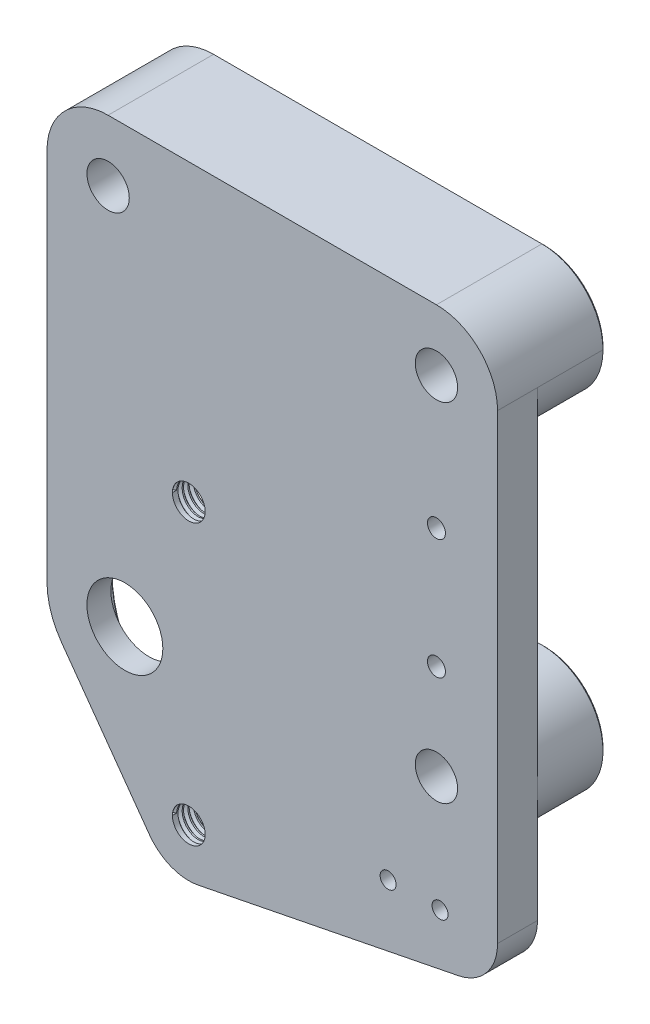
SolidWorks part; units mm, degrees
ref_plane "Front Plane" through (0, 0, 0) normal (0, 0, 1) x (1, 0, 0)
ref_plane "Top Plane" through (0, 0, 0) normal (0, 1, 0) x (1, 0, 0)
ref_plane "Right Plane" through (0, 0, 0) normal (1, 0, 0) x (0, 0, -1)
sketch "Sketch1" plane through (0, 0, 0) normal (0, 0, 1) x (1, 0, 0)
  line L0 (-41.1, 21.74) -> (0, 21.74) construction
  line L1 (0, 21.74) -> (0, -21.74) construction
  line L2 (-31, -25) -> (-39, -25) construction
  line L3 (-41, -23.5) -> (-37, -23.5) construction
  line L4 (-31, -25) -> (-12, -25) construction
  line L5 (-31, -25) -> (-31, -17.5) construction
  line L6 (-31, -17.5) -> (-12, -17.5) construction
  line L7 (-12, -25) -> (-12, -17.5) construction
  line L8 (-31, -25) -> (-12, -25) construction
  line L9 (-31, -25) -> (-31, -32.5) construction
  line L10 (-31, -32.5) -> (-12, -32.5) construction
  line L11 (-12, -25) -> (-12, -32.5) construction
  line L12 (-41, -26.5) -> (-37, -26.5) construction
  line L13 (-31, -42.5) -> (-31, -7.5) construction
  line L14 (-27.5, -7.5) -> (-27.5, -11.4446) construction
  line L15 (-34.5, -7.5) -> (-34.5, -11.4446) construction
  line L16 (-27.5, -42.5) -> (-27.5, -38.5554) construction
  line L17 (-34.5, -42.5) -> (-34.5, -38.5554) construction
  line L18 (0, -12.5249) -> (0, 12.4751) construction
  line L19 (-6, -12.5249) -> (6, -12.5249) construction
  line L20 (-6, -12.5249) -> (-6, 12.4751) construction
  line L21 (-6, 12.4751) -> (6, 12.4751) construction
  line L22 (6, -12.5249) -> (6, 12.4751) construction
  line L23 (-16.5, 74.5503) -> (-16.5, -75.4497) construction
  line L24 (-1.6, 12.4751) -> (1.6, 12.4751) construction
  line L25 (-1.6, 12.4751) -> (-1.6, 18.1751) construction
  line L26 (-1.6, 18.1751) -> (1.6, 18.1751) construction
  line L27 (1.6, 12.4751) -> (1.6, 18.1751) construction
  line L28 (-1.5, -12.5249) -> (1.5, -12.5249) construction
  line L29 (-1.5, -12.5249) -> (-1.5, -18.1749) construction
  line L30 (-1.5, -18.1749) -> (1.5, -18.1749) construction
  line L31 (1.5, -12.5249) -> (1.5, -18.1749) construction
  line L32 (6, 6.5051) -> (13.5, 6.5051) construction
  line L33 (6, 6.5051) -> (6, 10.9051) construction
  line L34 (6, 10.9051) -> (13.5, 10.9051) construction
  line L35 (13.5, 6.5051) -> (13.5, 10.9051) construction
  line L36 (-50, -10) -> (50, -10) construction
  line L37 (-50, -10) -> (-50, 10) construction
  line L38 (-50, 10) -> (50, 10) construction
  line L39 (50, -10) -> (50, 10) construction
  line L40 (-50, -10) -> (50, 10) construction
  line L41 (-50, 10) -> (50, -10) construction
  line L42 (-24, 74.5503) -> (-9, 74.5503) construction
  line L43 (-24, 74.5503) -> (-24, -75.4497) construction
  line L44 (-24, -75.4497) -> (-9, -75.4497) construction
  line L45 (-9, 74.5503) -> (-9, -75.4497) construction
  line L46 (-41.1, 29.39) -> (0, 29.39)
  line L47 (-35.916, -46.0264) -> (-46.9224, -30.6831)
  line L48 (-48.75, -25) -> (-48.75, 21.74)
  line L49 (-27.8523, -47.6667) -> (3.9802, -28.273)
  line L50 (7.65, 21.74) -> (7.65, -21.74)
  line L51 (-48.75, 14.09) -> (7.65, 14.09) construction
  line L52 (-7.05, -34.9931) -> (-7.05, -40.9931)
  line L53 (-7.05, -40.9931) -> (7.65, -40.9931)
  line L54 (7.65, -40.9931) -> (7.65, -12.4946)
  line L55 (0.45, -35.9931) -> (-6.05, -35.9931) construction
  line L56 (-29.8216, -48.4341) -> (7.65, -40.9931)
  circle A0 centre (-41.1, 21.74) radius 12 construction
  circle A1 centre (-41.1, 21.74) radius 2.65
  circle A2 centre (0, 21.74) radius 12 construction
  circle A3 centre (0, 21.74) radius 2.65
  circle A4 centre (0, -21.74) radius 12 construction
  circle A5 centre (0, -21.74) radius 2.65
  circle A6 centre (-31, -25) radius 14 construction
  circle A7 centre (-39, -25) radius 4.75
  circle A8 centre (-39, -25) radius 2.5 construction
  circle A9 centre (-31, -7.5) radius 2.05
  circle A10 centre (-31, -7.5) radius 3.5 construction
  circle A11 centre (-31, -42.5) radius 3.5 construction
  circle A12 centre (-31, -42.5) radius 2.05
  circle A13 centre (-39, -25) radius 15 construction
  circle A14 centre (0, -9.8249) radius 1 construction
  circle A15 centre (0, 5.1751) radius 1 construction
  circle A16 centre (-41.1, 21.74) radius 7.65
  circle A17 centre (0, 21.74) radius 7.65
  circle A18 centre (0, -21.74) radius 7.65
  circle A20 centre (-31, -42.5) radius 6.05
  circle A21 centre (-39, -25) radius 9.75
  circle A22 centre (-6.05, -35.9931) radius 1
  circle A23 centre (0.45, -35.9931) radius 1
  point P11 (0, 0)
  point P58 (6, 8.7051)
  point P66 (28.1399, 46.8209)
  dimension "D1" = 24
  dimension "D2" = 5.3
  dimension "D3" = 24
  dimension "D4" = 5.3
  dimension "D5" = 24
  dimension "D6" = 5.3
  dimension "D7" = 43.48
  dimension "D9" = 28
  dimension "D13" = 9.5
  dimension "D14" = 5
  dimension "D16" = 4.1
  dimension "D17" = 7
  dimension "D32" = 30
  dimension "D35" = 2
  dimension "D45" = 2
  dimension "D8" = 41.1
  dimension "D10" = 8
  dimension "D11" = 7.5
  dimension "D12" = 19
  dimension "D15" = 1.5
  dimension "D18" = 17.5
  dimension "D19" = 12
  dimension "D20" = 25
  dimension "D21" = 3.2
  dimension "D22" = 5.7
  dimension "D23" = 3
  dimension "D24" = 5.65
  dimension "D25" = 7.5
  dimension "D26" = 4.4
  dimension "D27" = 3.77
  dimension "D28" = 20
  dimension "D29" = 100
  dimension "D30" = 15
  dimension "D31" = 15
  dimension "D33" = 13
  dimension "D34" = 28
  dimension "D36" = 150
  dimension "D37" = 18.1751
  dimension "D42" = 39
  dimension "D43" = 14.7
  dimension "D44" = 6
  dimension "D46" = 1
  dimension "D47" = 5
  dimension "D38" = 5
  dimension "D39" = 5
  dimension "D40" = 4
  dimension "D41" = 5
extrude "Boss-Extrude1" add sketch "Sketch1" along normal blind 5 contours A21 L47 A20 L49 A18 L50 A17 L46 A16 L48 A9 | A16 A1 | A17 A3 | A18 A5 | A20 A12 | A21 A7 | A18 L49 L52 L53 L54 | L49 A20 L56 L53 L52 region at (-20.5785, -3.8476, 0) region at (-35.8436, 26.9964, 0) region at (5.2564, 26.9964, 0) region at (-39, -15.5258, 0) region at (6.4811, -25.3806, 0) region at (1.6273, -35.2213, 0) region at (-32.7998, -36.9034, 0) region at (-12.0976, -42.3056, 0)
sketch "Sketch2" plane through (0, 0, 0) normal (0, 0, -1) x (-1, 0, 0)
  line L0 (48.75, 14.09) -> (-7.65, 14.09) construction
  line L1 (48.75, 14.09) -> (-7.65, 14.09)
  circle A0 centre (0, -21.74) radius 7.65 construction
  circle A1 centre (31, -42.5) radius 2.05
  circle A2 centre (31, -42.5) radius 2.05
  circle A3 centre (39, -25) radius 4.75
  circle A4 centre (39, -25) radius 4.75
  circle A5 centre (0, -21.74) radius 2.65
  circle A6 centre (0, -21.74) radius 2.65
  circle A7 centre (0, 21.74) radius 2.65
  circle A8 centre (0, 21.74) radius 2.65
  circle A9 centre (41.1, 21.74) radius 2.65
  circle A10 centre (41.1, 21.74) radius 2.65
  circle A11 centre (31, -7.5) radius 2.05
  circle A12 centre (31, -7.5) radius 2.05
  circle A13 centre (0, -21.74) radius 7.65
  line M7 (48.75, -25) -> (48.75, 21.74)
  arc M8 (48.75, 21.74) -> (41.1, 29.39) centre (41.1, 21.74) ccw
  line M9 (41.1, 29.39) -> (0, 29.39)
  arc M10 (0, 29.39) -> (-7.65, 21.74) centre (0, 21.74) ccw
  line M11 (-7.65, 21.74) -> (-7.65, -40.9931)
  circle M18 centre (41.1, 21.74) radius 2.65
  circle M19 centre (0, 21.74) radius 2.65
  circle M20 centre (0, -21.74) radius 2.65
  dimension "D1" = 0
  dimension "D2" = 0
  dimension "D3" = 0
  dimension "D4" = 0
  dimension "D5" = 0
  dimension "D6" = 0
extrude "Boss-Extrude2" add sketch "Sketch2" along normal blind 8.5 contours L1 M7 M8 M9 M10 M11 M19 M18 | A13 M20 region at (0, -14.3064, 0) region at (-20.55, 21.552, 0)
sketch "Sketch7" plane through (0, 0, 0) normal (0, 0, -1) x (-1, 0, 0)
  line L0 (27.5, -42.5) -> (27.5, -38.5554) construction
  line L1 (34.5, -42.5) -> (34.5, -38.5554) construction
  line L2 (27.5, -7.5) -> (27.5, -11.4446) construction
  line L3 (34.5, -7.5) -> (34.5, -11.4446) construction
  line L4 (27.5, -42.5) -> (27.5, -38.5554)
  line L5 (34.5, -42.5) -> (34.5, -38.5554)
  line L6 (27.5, -7.5) -> (27.5, -11.4446)
  line L7 (34.5, -7.5) -> (34.5, -11.4446)
  line L12 (12, -25) -> (12, -32.5) construction
  line L13 (31, -32.5) -> (12, -32.5) construction
  line L14 (12, -25) -> (12, -17.5) construction
  line L15 (31, -17.5) -> (12, -17.5) construction
  line L16 (12, -25) -> (12, -32.5)
  line L17 (19.1784, -32.5) -> (12, -32.5)
  line L18 (12, -25) -> (12, -17.5)
  line L19 (19.1784, -17.5) -> (12, -17.5)
  line L20 (19.0146, -17.2) -> (11.7, -17.2)
  line L21 (11.7, -25) -> (11.7, -17.2)
  line L22 (11.7, -25) -> (11.7, -32.8)
  line L23 (19.0146, -32.8) -> (11.7, -32.8)
  line L24 (27.2, -42.5) -> (27.2, -38.7859)
  line L25 (34.8, -42.5) -> (34.8, -38.7859)
  line L26 (34.8, -7.5) -> (34.8, -11.2141)
  line L27 (27.2, -7.5) -> (27.2, -11.2141)
  circle A0 centre (31, -42.5) radius 3.5 construction
  circle A1 centre (31, -7.5) radius 3.5 construction
  circle A2 centre (31, -25) radius 14 construction
  arc A3 (27.5, -42.5) -> (34.5, -42.5) centre (31, -42.5) ccw
  arc A4 (34.5, -7.5) -> (27.5, -7.5) centre (31, -7.5) ccw
  arc A5 (34.5, -38.5554) -> (34.5, -11.4446) centre (31, -25) ccw
  arc A6 (27.5, -11.4446) -> (19.1784, -17.5) centre (31, -25) ccw
  arc A11 (19.1784, -32.5) -> (27.5, -38.5554) centre (31, -25) ccw
  arc A12 (27.2, -11.2141) -> (19.0146, -17.2) centre (31, -25) ccw
  arc A13 (19.0146, -32.8) -> (27.2, -38.7859) centre (31, -25) ccw
  arc A14 (27.2, -42.5) -> (34.8, -42.5) centre (31, -42.5) ccw
  arc A15 (34.8, -38.7859) -> (34.8, -11.2141) centre (31, -25) ccw
  arc A16 (34.8, -7.5) -> (27.2, -7.5) centre (31, -7.5) ccw
  circle M9 centre (31, -7.5) radius 2.05
  circle M10 centre (31, -42.5) radius 2.05
  circle M11 centre (39, -25) radius 4.75
  dimension "D1" = 0.3
extrude "Cut-Extrude1" cut sketch "Sketch7" against normal blind 2 contours L6 A6 L4 A3 L5 A5 L7 A4 M10 M11 M9 | A12 L19 A6 L6 A4 L7 A5 L5 A3 L4 region at (-28.1953, -25, 0) region at (-22.5909, -13.5009, 0)
fillet "Fillet1" radius 2 8 edges at (-19.0146, -32.8, 1) (-34.8, -38.7859, 1) (-27.2, -38.7859, 1) (-34.8, -11.2141, 1) (-27.2, -11.2141, 1) (-19.0146, -17.2, 1) (-11.7, -32.8, 1) (-11.7, -17.2, 1)
thread "Thread1" pitch 0.7 method cut profile "Thread Profile1" start angle 0, offset 0, length 10, pitch 0.7, diameter 4.1
ref_plane "Plane1" through (-33.05, -7.5, 5) normal (0, -1, 0) x (-1, 0, 0)
sketch "Thread Profile1" plane through (-33.05, -7.5, 5) normal (0, -1, 0) x (-1, 0, 0)
  line L0 (0, 0) -> (0, 0.7) construction
  line L1 (0, 0) -> (0.3789, 0.2187)
  line L2 (0.3789, 0.2187) -> (0.3789, 0.3062)
  line L3 (0.3789, 0.3062) -> (0, 0.525)
  line L4 (0.3789, 0.2625) -> (0, 0.2625) construction
  line L11 (0, 0) -> (0, 0.525)
  point P2 (0, 0)
  dimension "Pitch" = 0.7
  dimension "Profile_Angle" = 60
  dimension "Profile_Land" = 0.0875
  dimension "Profile_Height" = 0.3789
thread "Thread2" pitch 0.7 method cut profile "Thread Profile2" start angle 0, offset 0, length 10, pitch 0.7, diameter 4.1
ref_plane "Plane2" through (-33.05, -42.5, 5) normal (0, -1, 0) x (-1, 0, 0)
sketch "Thread Profile2" plane through (-33.05, -42.5, 5) normal (0, -1, 0) x (-1, 0, 0)
  line L0 (0, 0) -> (0, 0.7) construction
  line L1 (0, 0) -> (0.3789, 0.2187)
  line L2 (0.3789, 0.2187) -> (0.3789, 0.3062)
  line L3 (0.3789, 0.3062) -> (0, 0.525)
  line L4 (0.3789, 0.2625) -> (0, 0.2625) construction
  line L11 (0, 0) -> (0, 0.525)
  point P2 (0, 0)
  dimension "Pitch" = 0.7
  dimension "Profile_Angle" = 60
  dimension "Profile_Land" = 0.0875
  dimension "Profile_Height" = 0.3789
fillet "Fillet2" radius 7.65 2 edges at (7.65, 14.09, -4.25) (-48.75, 14.09, -4.25)
sketch "Sketch10" plane through (0, 0, -8.5) normal (0, 0, -1) x (-1, 0, 0)
  line L0 (0, 14.09) -> (41.1, 14.09) construction
  line L1 (41.1, 29.39) -> (0, 29.39) construction
  line L2 (0, 14.09) -> (41.1, 14.09)
  line L3 (41.1, 29.39) -> (0, 29.39)
  circle A1 centre (0, -21.74) radius 2.65
  circle A2 centre (0, -21.74) radius 2.65
  circle A3 centre (41.1, 21.74) radius 2.65
  circle A4 centre (41.1, 21.74) radius 2.65
  circle A5 centre (0, 21.74) radius 2.65
  circle A6 centre (0, 21.74) radius 2.65
  arc A7 (0, 29.39) -> (-7.65, 21.74) centre (0, 21.74) ccw construction
  arc A8 (-7.65, 21.74) -> (0, 14.09) centre (0, 21.74) ccw construction
  arc A9 (41.1, 14.09) -> (48.75, 21.74) centre (41.1, 21.74) ccw construction
  arc A10 (48.75, 21.74) -> (41.1, 29.39) centre (41.1, 21.74) ccw construction
  arc A12 (0, 29.39) -> (-7.65, 21.74) centre (0, 21.74) ccw
  arc A13 (-7.65, 21.74) -> (0, 14.09) centre (0, 21.74) ccw
  arc A14 (41.1, 14.09) -> (48.75, 21.74) centre (41.1, 21.74) ccw
  arc A15 (48.75, 21.74) -> (41.1, 29.39) centre (41.1, 21.74) ccw
  circle A16 centre (0, 21.74) radius 4
  circle A17 centre (41.1, 21.74) radius 4
  circle A18 centre (0, -21.74) radius 4
  circle M10 centre (0, 21.74) radius 2.65
  circle M11 centre (41.1, 21.74) radius 2.65
  dimension "D4" = 8
  dimension "D5" = 8
  dimension "D1" = 0
  dimension "D2" = 0
  dimension "D3" = 0
extrude "Boss-Extrude5" add sketch "Sketch10" along normal blind 1 contours A18 A2 | M10 | A17 M11 | A16 region at (0, 21.74, -8.5) region at (-37.2131, 21.74, -8.5) region at (3.8869, -21.74, -8.5)
chamfer "Chamfer2" distance 0.3 angle 45 30 edges at (-20.55, 14.09, -8.5) (-46.5094, 16.3306, -8.5) (5.4094, 16.3306, -8.5) (-46.5094, 27.1494, -8.5) (5.4094, 27.1494, -8.5) (-20.55, 29.39, -8.5) (-4, -21.74, -8.5) (-4, 21.74, -8.5) (-45.1, 21.74, -8.5) (-22.4054, -13.571, 0) (-7.65, -21.74, -8.5) (-11.7, -25, 0) (-15.8375, -17.2, 0) (-18.8681, -16.9895, 0) (-26.8467, -10.9019, 0) (-27.2, -8.6334, 0) (-31, -3.7, 0) (-34.8, -8.6334, 0) (-35.1533, -10.9019, 0) (-45.3, -25, 0) (-35.1533, -39.0981, 0) (-34.8, -41.3666, 0) (-31, -46.3, 0) (-15.8375, -32.8, 0) (-27.2, -41.3666, 0) (-18.8681, -33.0105, 0) (-26.8467, -39.0981, 0) (-22.4054, -36.429, 0) (-12.2858, -17.7858, 0) (-12.2858, -32.2142, 0)
sketch "Sketch11" plane through (0, 0, 5) normal (0, 0, 1) x (1, 0, 0)
  circle A0 centre (0, 5.1751) radius 1.125
  circle A1 centre (0, -9.8249) radius 1.125
  point P0 (0, -9.8249)
  point P2 (0, 5.1751)
  dimension "D1" = 2.25
extrude "Cut-Extrude3" cut sketch "Sketch11" against normal blind 10
sketch "Sketch12" plane through (0, 0, 0) normal (0, 0, -1) x (-1, 0, 0)
  circle A0 centre (0, 5.1751) radius 2
  circle A1 centre (0, -9.8249) radius 2
  dimension "D1" = 4
extrude "Cut-Extrude4" cut sketch "Sketch12" against normal blind 2
fillet "Fillet3" radius 6.05 1 edges at (7.65, -40.9931, 2.5)
